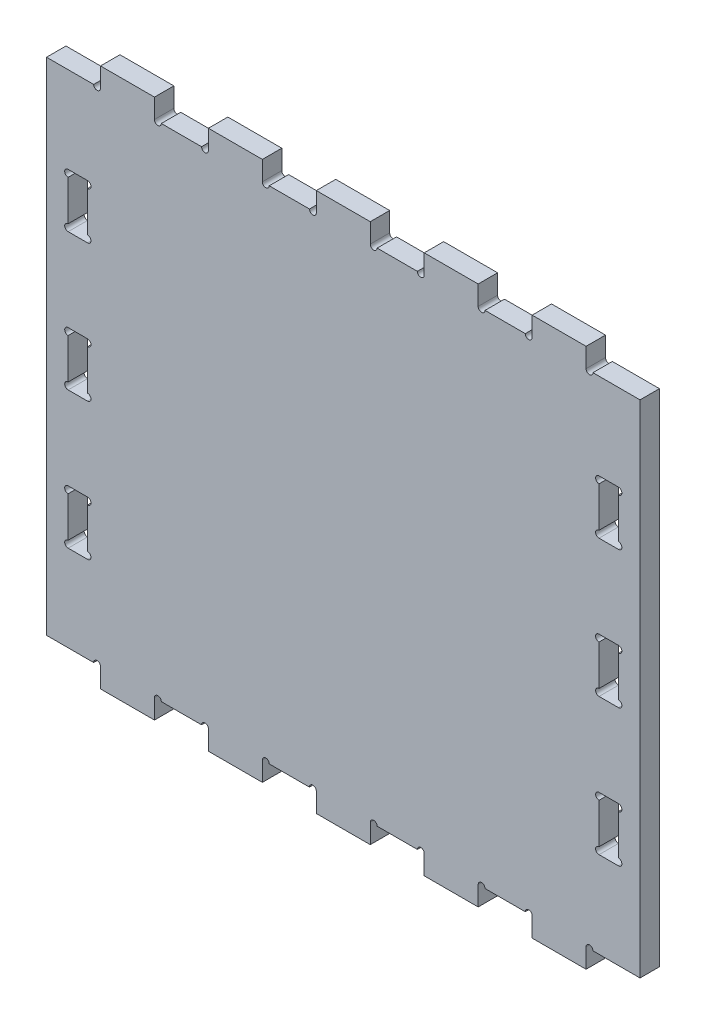
SolidWorks part; units mm, degrees
ref_plane "Piano frontale" through (0, 0, 0) normal (0, 0, 1) x (1, 0, 0)
ref_plane "Piano superiore" through (0, 0, 0) normal (0, 1, 0) x (1, 0, 0)
ref_plane "Piano destro" through (0, 0, 0) normal (1, 0, 0) x (0, 0, -1)
sketch "Model" plane through (0, 0, 0) normal (0, 0, 1) x (1, 0, 0)
  line L0 (-255, 145.65) -> (-255, 108.35)
  line L1 (-255, 102) -> (-237, 102)
  line L2 (-237, 145.65) -> (-237, 108.35)
  line L3 (-255, 152) -> (-237, 152)
  line L4 (237, 145.65) -> (237, 108.35)
  line L5 (255, 102) -> (237, 102)
  line L6 (255, 145.65) -> (255, 108.35)
  line L7 (255, 152) -> (237, 152)
  line L8 (0, 0) -> (504.1303, 0) construction
  line L9 (-275, -232) -> (-275, 232)
  line L10 (-25, 250) -> (25, 250)
  line L11 (-225, 250) -> (-225, 232)
  line L12 (-68.65, 232) -> (-31.35, 232)
  line L13 (-175, 232) -> (-175, 250)
  line L14 (31.35, 232) -> (68.65, 232)
  line L15 (-125, 250) -> (-125, 232)
  line L16 (75, 250) -> (125, 250)
  line L17 (-75, 232) -> (-75, 250)
  line L18 (131.35, 232) -> (168.65, 232)
  line L19 (-25, 250) -> (-25, 232)
  line L20 (175, 250) -> (225, 250)
  line L21 (25, 232) -> (25, 250)
  line L22 (231.35, 232) -> (275, 232)
  line L23 (75, 250) -> (75, 232)
  line L24 (-275, 232) -> (-231.35, 232)
  line L25 (125, 232) -> (125, 250)
  line L26 (231.35, -232) -> (275, -232)
  line L27 (175, 250) -> (175, 232)
  line L28 (-275, -232) -> (-231.35, -232)
  line L29 (225, 232) -> (225, 250)
  line L30 (-125, -250) -> (-75, -250)
  line L31 (275, 232) -> (275, -232)
  line L32 (-168.65, -232) -> (-131.35, -232)
  line L33 (-225, -250) -> (-175, -250)
  line L34 (225, -232) -> (225, -250)
  line L35 (175, -250) -> (175, -232)
  line L36 (125, -232) -> (125, -250)
  line L37 (75, -250) -> (75, -232)
  line L38 (25, -232) -> (25, -250)
  line L39 (175, -250) -> (225, -250)
  line L40 (-25, -250) -> (-25, -232)
  line L41 (131.35, -232) -> (168.65, -232)
  line L42 (-75, -232) -> (-75, -250)
  line L43 (75, -250) -> (125, -250)
  line L44 (-125, -250) -> (-125, -232)
  line L45 (31.35, -232) -> (68.65, -232)
  line L46 (-175, -232) -> (-175, -250)
  line L47 (-68.65, -232) -> (-31.35, -232)
  line L48 (-225, -250) -> (-225, -232)
  line L49 (-25, -250) -> (25, -250)
  line L52 (237, -18.65) -> (237, 18.65)
  line L53 (255, -25) -> (237, -25)
  line L54 (255, -18.65) -> (255, 18.65)
  line L55 (255, 25) -> (237, 25)
  line L56 (237, -145.65) -> (237, -108.35)
  line L57 (255, -152) -> (237, -152)
  line L58 (255, -145.65) -> (255, -108.35)
  line L59 (255, -102) -> (237, -102)
  line L60 (-255, -18.65) -> (-255, 18.65)
  line L61 (-255, -25) -> (-237, -25)
  line L62 (-237, -18.65) -> (-237, 18.65)
  line L63 (-255, 25) -> (-237, 25)
  line L64 (-255, -145.65) -> (-255, -108.35)
  line L65 (-255, -152) -> (-237, -152)
  line L66 (-237, -145.65) -> (-237, -108.35)
  line L67 (-255, -102) -> (-237, -102)
  line L69 (-225, 250) -> (-175, 250)
  line L70 (-168.65, 232) -> (-131.35, 232)
  line L71 (-125, 250) -> (-75, 250)
  arc A0 (-255, 152) -> (-255, 145.65) centre (-255, 148.825) ccw
  arc A1 (-255, 108.35) -> (-255, 102) centre (-255, 105.175) ccw
  arc A2 (-237, 102) -> (-237, 108.35) centre (-237, 105.175) ccw
  arc A3 (-237, 145.65) -> (-237, 152) centre (-237, 148.825) ccw
  arc A4 (237, 152) -> (237, 145.65) centre (237, 148.825) ccw
  arc A5 (237, 108.35) -> (237, 102) centre (237, 105.175) ccw
  arc A6 (255, 102) -> (255, 108.35) centre (255, 105.175) ccw
  arc A7 (255, 145.65) -> (255, 152) centre (255, 148.825) ccw
  arc A8 (-131.35, 232) -> (-125, 232) centre (-128.175, 232) ccw
  arc A9 (-175, 232) -> (-168.65, 232) centre (-171.825, 232) ccw
  arc A10 (-31.35, 232) -> (-25, 232) centre (-28.175, 232) ccw
  arc A11 (-75, 232) -> (-68.65, 232) centre (-71.825, 232) ccw
  arc A12 (68.65, 232) -> (75, 232) centre (71.825, 232) ccw
  arc A13 (25, 232) -> (31.35, 232) centre (28.175, 232) ccw
  arc A14 (168.65, 232) -> (175, 232) centre (171.825, 232) ccw
  arc A15 (125, 232) -> (131.35, 232) centre (128.175, 232) ccw
  arc A16 (-231.35, -232) -> (-225, -232) centre (-228.175, -232) cw
  arc A17 (225, 232) -> (231.35, 232) centre (228.175, 232) ccw
  arc A18 (225, -232) -> (231.35, -232) centre (228.175, -232) cw
  arc A19 (125, -232) -> (131.35, -232) centre (128.175, -232) cw
  arc A20 (168.65, -232) -> (175, -232) centre (171.825, -232) cw
  arc A21 (25, -232) -> (31.35, -232) centre (28.175, -232) cw
  arc A22 (68.65, -232) -> (75, -232) centre (71.825, -232) cw
  arc A23 (-75, -232) -> (-68.65, -232) centre (-71.825, -232) cw
  arc A24 (-31.35, -232) -> (-25, -232) centre (-28.175, -232) cw
  arc A25 (-175, -232) -> (-168.65, -232) centre (-171.825, -232) cw
  arc A26 (-131.35, -232) -> (-125, -232) centre (-128.175, -232) cw
  arc A28 (237, -18.65) -> (237, -25) centre (237, -21.825) ccw
  arc A29 (255, -25) -> (255, -18.65) centre (255, -21.825) ccw
  arc A30 (255, 18.65) -> (255, 25) centre (255, 21.825) ccw
  arc A31 (237, 25) -> (237, 18.65) centre (237, 21.825) ccw
  arc A32 (237, -145.65) -> (237, -152) centre (237, -148.825) ccw
  arc A33 (255, -152) -> (255, -145.65) centre (255, -148.825) ccw
  arc A34 (255, -108.35) -> (255, -102) centre (255, -105.175) ccw
  arc A35 (237, -102) -> (237, -108.35) centre (237, -105.175) ccw
  arc A36 (-255, -18.65) -> (-255, -25) centre (-255, -21.825) ccw
  arc A37 (-237, -25) -> (-237, -18.65) centre (-237, -21.825) ccw
  arc A38 (-237, 18.65) -> (-237, 25) centre (-237, 21.825) ccw
  arc A39 (-255, 25) -> (-255, 18.65) centre (-255, 21.825) ccw
  arc A40 (-255, -145.65) -> (-255, -152) centre (-255, -148.825) ccw
  arc A41 (-237, -152) -> (-237, -145.65) centre (-237, -148.825) ccw
  arc A42 (-237, -108.35) -> (-237, -102) centre (-237, -105.175) ccw
  arc A43 (-255, -102) -> (-255, -108.35) centre (-255, -105.175) ccw
  arc A45 (-231.35, 232) -> (-225, 232) centre (-228.175, 232) ccw
  arc A46 (268.65, 232) -> (275, 232) centre (271.825, 232) ccw [skipped]
  point P132 (-253.175, 232)
  dimension "D2" = 500
  dimension "D3" = 80
  dimension "D4" = 80
  dimension "D5" = 77
  dimension "D6" = 77
  dimension "D1" = 6
extrude "Estrusione-Estrusione1" add sketch "Model" along normal blind 18 contours L70 A8 L15 L71 L17 A11 L12 A10 L19 L10 L21 A13 L14 A12 L23 L16 L25 A15 L18 A14 L27 L20 L29 A17 L22 L31 L26 A18 L34 L39 L35 A20 L41 A19 L36 L43 L37 A22 L45 A21 L38 L49 L40 A24 L47 A23 L42 L30 L44 A26 L32 A25 L46 L33 L48 A16 L28 L9 L24 A45 L11 L69 L13 A9
extrude "Taglio-Estrusione1" cut sketch "Model<3>" along normal blind 47 contours L2 A2 L1 A1 L0 A0 L3 A3
sketch "Model<3>" plane through (0, 0, 0) normal (0, 0, 1) x (1, 0, 0) same geometry as "Model"
extrude "Taglio-Estrusione2" cut sketch "Model<4>" along normal blind 32 contours L62 A38 L63 A39 L60 A36 L61 A37
sketch "Model<4>" plane through (0, 0, 0) normal (0, 0, 1) x (1, 0, 0) same geometry as "Model"
extrude "Taglio-Estrusione3" cut sketch "Model<5>" along normal blind 50 contours L66 A42 L67 A43 L64 A40 L65 A41
sketch "Model<5>" plane through (0, 0, 0) normal (0, 0, 1) x (1, 0, 0) same geometry as "Model"
extrude "Taglio-Estrusione4" cut sketch "Model<6>" along normal blind 44 contours L4 A5 L5 A6 L6 A7 L7 A4
sketch "Model<6>" plane through (0, 0, 0) normal (0, 0, 1) x (1, 0, 0) same geometry as "Model"
extrude "Taglio-Estrusione5" cut sketch "Model<7>" along normal blind 38 contours L54 A30 L55 A31 L52 A28 L53 A29
sketch "Model<7>" plane through (0, 0, 0) normal (0, 0, 1) x (1, 0, 0) same geometry as "Model"
extrude "Taglio-Estrusione6" cut sketch "Model<10>" along normal blind 44 contours L56 A35 L59 A34 L58 A33 L57 A32
sketch "Model<10>" plane through (0, 0, 0) normal (0, 0, 1) x (1, 0, 0) same geometry as "Model"
